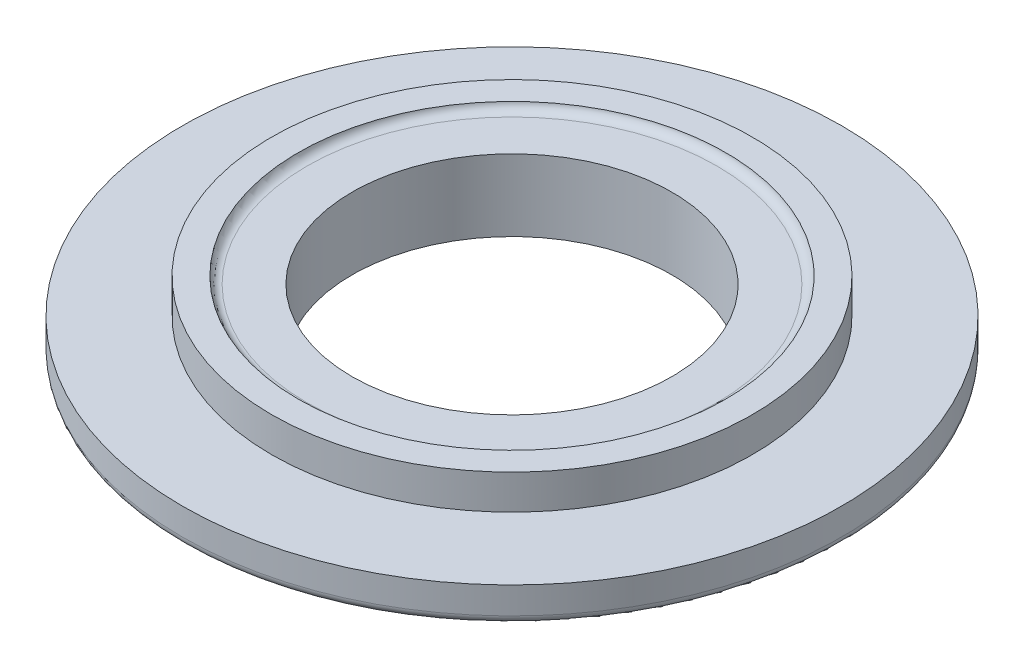
SolidWorks part; units mm, degrees
ref_plane "Front Plane" through (0, 0, 0) normal (0, 0, 1) x (1, 0, 0)
ref_plane "Top Plane" through (0, 0, 0) normal (0, 1, 0) x (1, 0, 0)
ref_plane "Right Plane" through (0, 0, 0) normal (1, 0, 0) x (0, 0, -1)
sketch "Sketch1" plane through (0, 0, 0) normal (0, 0, 1) x (1, 0, 0)
  line L0 (7.3061, -0.8272) -> (7.3061, -14.7207)
  line L1 (7.3061, -14.7207) -> (3.9534, -14.7207)
  line L2 (3.9534, -14.7207) -> (3.9534, -6.1207)
  line L3 (3.9534, -6.1207) -> (-1.5618, -6.1207)
  line L4 (-1.5618, -6.1207) -> (-1.5618, -13.0207)
  line L5 (-1.5618, -13.0207) -> (-25.5836, -13.0207)
  line L6 (-25.5836, -13.0207) -> (-25.5836, -6.1207)
  line L7 (-25.5836, -6.1207) -> (-8.3026, -6.1207)
  line L8 (-8.3026, -6.1207) -> (-8.3026, 0.6027)
  line L9 (-8.3026, 0.6027) -> (-3.1142, 0.6027)
  line L10 (-3.1142, 0.6027) -> (-3.1142, -0.8272)
  line L11 (-3.1142, -0.8272) -> (7.3061, -0.8272)
  line L12 (38.3061, 0.6027) -> (38.3061, -14.7207)
  point P12 (38.3718, -14.7207)
  point P15 (0, 0)
  point P16 (0, 0.8886)
  point P17 (0, 0)
  point P18 (38.3061, 0.6027)
  dimension "D1" = 31
revolve "Revolve2" add sketch "Sketch1" angle 360 about L12 region at (-7.6271, -7.6404, 0)
fillet "Fillet3" radius 1.7 1 edges at (38.3061, -0.8272, 41.4203)
fillet "Fillet4" radius 1.7 1 edges at (38.3061, -13.0207, 63.8897)
